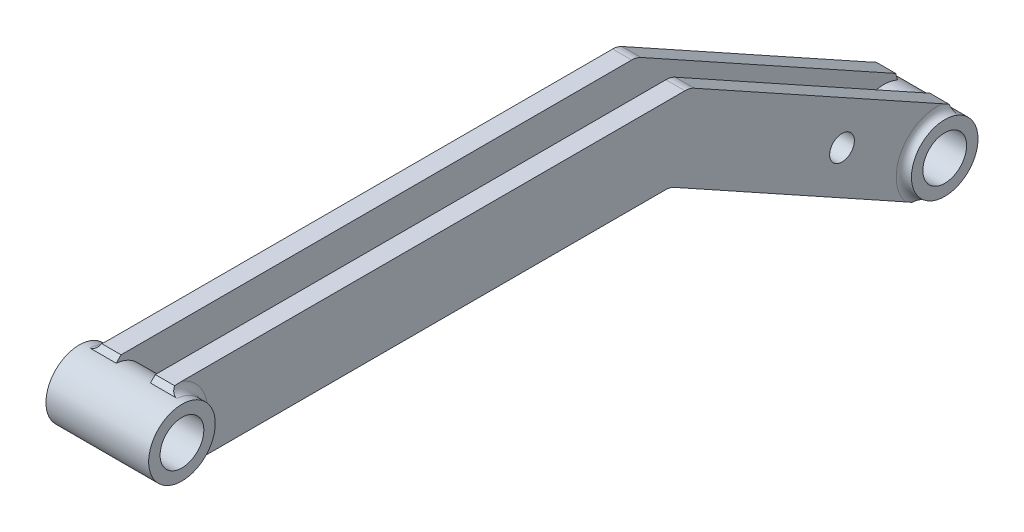
SolidWorks part; units mm, degrees
material "1.0044 (S275JR)"
ref_plane "Płaszczyzna przednia" through (0, 0, 0) normal (0, 0, 1) x (1, 0, 0)
ref_plane "Płaszczyzna górna" through (0, 0, 0) normal (0, 1, 0) x (1, 0, 0)
ref_plane "Płaszczyzna prawa" through (0, 0, 0) normal (1, 0, 0) x (0, 0, -1)
sketch "Szkic1" plane through (0, 0, 0) normal (1, 0, 0) x (0, 0, -1)
  line L0 (0, 0) -> (271, 0)
  line L1 (271, 0) -> (407.1977, -75.4956)
  line L2 (407.1977, -75.4956) -> (408.757, -80.9333)
  line L3 (408.757, -80.9333) -> (393.243, -108.9212)
  line L4 (393.243, -108.9212) -> (387.8053, -110.4804)
  line L5 (387.8053, -110.4804) -> (260.6553, -40)
  line L6 (260.6553, -40) -> (0, -40)
  line L7 (0, -40) -> (-4, -36)
  line L8 (-4, -36) -> (-4, -4)
  line L9 (-4, -4) -> (0, 0)
  point P14 (401, -94.9273)
  dimension "D1" = 45
  dimension "D2" = 45
  dimension "D3" = 40
  dimension "D4" = 32
  dimension "D5" = 40
  dimension "D6" = 151
  dimension "D7" = 130
  dimension "D8" = 32
  dimension "D9" = 45
  dimension "D10" = 45
  dimension "D11" = 275
extrude "Dodanie-wyciągnięcie1" add sketch "Szkic1" along normal blind 10
ref_plane "Płaszczyzna1" through (-9, 0, 0) normal (-1, 0, 0) x (0, 0, 1)
mirror "Lustro3" about plane through (-9, 0, 0) normal (-1, 0, 0) of bodies 101
sketch "Szkic2" plane through (10, 0, 0) normal (1, 0, 0) x (0, 0, -1)
  line L0 (-4, -4) -> (-4, -36) construction
  circle A0 centre (-4, -20) radius 17.5
  dimension "D1" = 35
extrude "Dodanie-wyciągnięcie2" add sketch "Szkic2" along normal blind 8 and the other way blind 46
sketch "Szkic3" plane through (10, 0, 0) normal (1, 0, 0) x (0, 0, -1)
  line L0 (393.243, -108.9212) -> (408.757, -80.9333) construction
  circle A0 centre (401, -94.9273) radius 17.5
  dimension "D1" = 35
extrude "Dodanie-wyciągnięcie3" add sketch "Szkic3" along normal blind 4 and the other way blind 42
sketch "Szkic4" plane through (18, 0, 0) normal (1, 0, 0) x (0, 0, -1)
  circle A0 centre (-4, -20) radius 11.5
  dimension "D1" = 23
extrude "Wytnij-wyciągnięcie1" cut sketch "Szkic4" against normal up to next
sketch "Szkic5" plane through (14, 0, 0) normal (1, 0, 0) x (0, 0, -1)
  circle A0 centre (401, -94.9273) radius 11.5
  dimension "D1" = 23
extrude "Wytnij-wyciągnięcie2" cut sketch "Szkic5" against normal up to next
fillet "Zaokrąglenie1" radius 4 4 edges at (-28, -86.4431, -385.6942) (-28, -20, -13.5) (10, -20, -13.5) (10, -86.4431, -385.6942)
fillet "Zaokrąglenie2" radius 10 4 edges at (-23, -40, -260.6553) (5, -40, -260.6553) (-23, 0, -271) (5, 0, -271)
sketch "Szkic7" plane through (10, 0, 0) normal (1, 0, 0) x (0, 0, -1)
  line L0 (403.7956, -73.6098) -> (273.2619, -1.2538) construction
  circle A0 centre (351, -67.2118) radius 6.5
  dimension "D1" = 13
  dimension "D2" = 20
  dimension "D3" = 50
extrude "Wytnij-wyciągnięcie3" cut sketch "Szkic7" against normal through all
